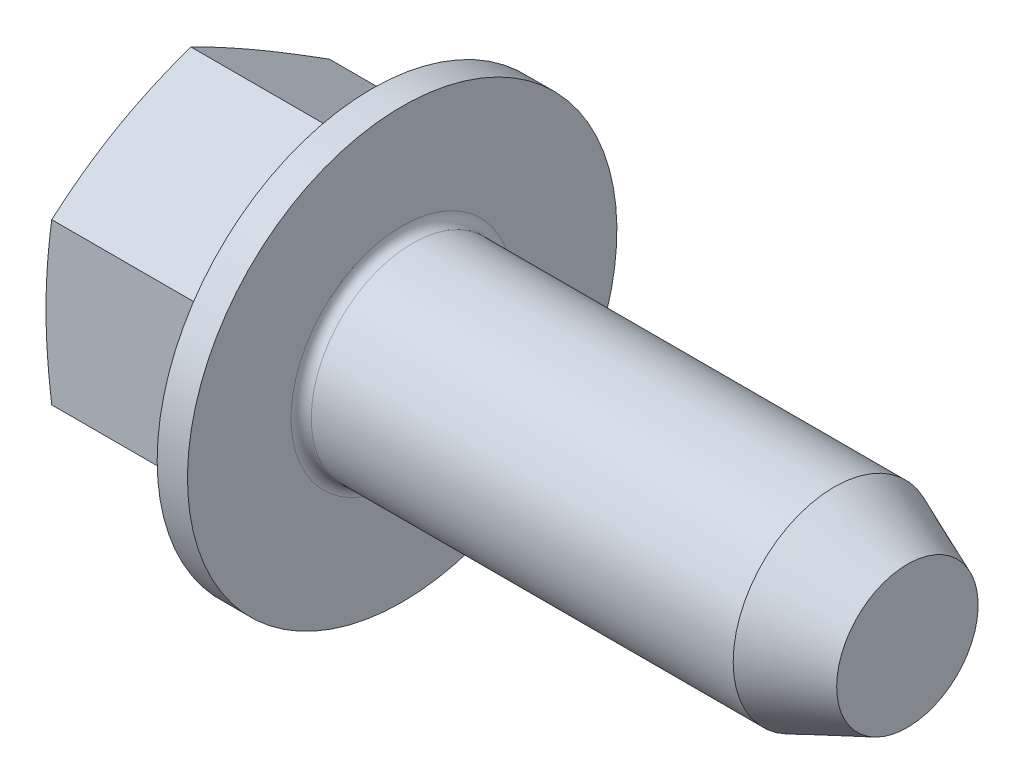
SolidWorks part; units mm, degrees
ref_plane "Front Plane" through (0, 0, 0) normal (0, 0, 1) x (1, 0, 0)
ref_plane "Top Plane" through (0, 0, 0) normal (0, 1, 0) x (1, 0, 0)
ref_plane "Right Plane" through (0, 0, 0) normal (1, 0, 0) x (0, 0, -1)
sketch "Sketch1" plane through (0, 0, 0) normal (0, 0, 1) x (1, 0, 0)
  line L0 (0, 0) -> (10, 0) construction
  line L1 (0, 0) -> (-4.3, 0) construction
  line L2 (0.2, 2) -> (9.61, 2)
  line L3 (10, 0) -> (10, 1.61)
  line L4 (0, 2.2) -> (0, 4.25)
  line L5 (0, 4.25) -> (-0.6, 4.25)
  line L6 (-0.6, 4.25) -> (-1.0019, 2.75)
  line L7 (-1.0019, 2.75) -> (-4.3, 2.75)
  line L8 (-4.3, 2.75) -> (-4.3, 2.2)
  line L9 (-4.3, 2.2) -> (-3.7625, 2.2)
  line L10 (-3.7625, 2.2) -> (-3.7625, 0)
  line L11 (-3.7625, 0) -> (10, 0)
  line L12 (-3.7625, 0) -> (-3.7625, 2.58) construction
  line L14 (10, 1.61) -> (9.61, 2)
  line L15 (10, 0) -> (0.7, 0) construction
  arc A0 (0.2, 2) -> (0, 2.2) centre (0.2, 2.2) cw
  dimension "D7" = 0.2
  dimension "K" = 4.3
  dimension "s" = 5.5
  dimension "dia" = 4
  dimension "D1" = 4.4
  dimension "D2" = 0.5375
  dimension "c" = 0.6
  dimension "D4" = 15
  dimension "D5" = 45
  dimension "min" = 3.22
  dimension "Dc" = 8.5
revolve "Revolve1" add sketch "Sketch1" angle 360 about L11
cosmetic thread "Cosmetic Thread1" [suppressed] parameters "D1"=14.01, "D2"=3.22
sketch "Sketch2" plane through (-4.3, 0, 0) normal (-1, 0, 0) x (0, 0, 1)
  line L1 (0, 3.1754) -> (-2.75, 1.5877)
  line L2 (-2.75, 1.5877) -> (-2.75, -1.5877)
  line L3 (-2.75, -1.5877) -> (0, -3.1754)
  line L4 (0, -3.1754) -> (2.75, -1.5877)
  line L5 (2.75, -1.5877) -> (2.75, 1.5877)
  line L6 (2.75, 1.5877) -> (0, 3.1754)
  circle A0 centre (0, 0) radius 2.2 construction
  circle A1 centre (0, 0) radius 2.2
  circle A2 centre (0, 0) radius 2.75 construction
  circle A3 centre (0, 0) radius 2.75 construction
extrude "Extrude1" add sketch "Sketch2" against normal up to next (4.3 mm away)
sketch "Sketch3" plane through (0, 0, 0) normal (0, 1, 0) x (1, 0, 0)
  line L0 (-4.6684, 1.375) -> (-3.9316, 4.125)
  line L1 (-4.3, 0) -> (-4.3, 2.75) construction
  line L2 (0, 0) -> (-3.6033, 0) construction
  line L3 (-3.9316, 4.125) -> (-4.6684, 4.125)
  line L4 (-4.6684, 4.125) -> (-4.6684, 1.375)
  dimension "D1" = 15
  dimension "D2" = 2.75
revolve "Cut-Revolve1" cut sketch "Sketch3" angle 360 about L2
fillet "Fillet1" radius 0.2 6 edges
sketch "Sketch4" plane through (0, 0, 0) normal (0, 0, 1) x (1, 0, 0)
  line L0 (0, 0) -> (5.3731, 0) construction
  line L1 (10, -1.61) -> (10, 1.61) construction
  line L3 (10, 1.4) -> (8.5515, 2)
  line L4 (0.2, 2) -> (9.61, 2) construction
  line L5 (8.5515, 2) -> (8.5515, 2.5)
  line L6 (8.5515, 2.5) -> (10, 2.5)
  line L7 (10, 2.5) -> (10, 1.4)
  dimension "D1" = 0.5
  dimension "D2" = 22.5
  dimension "Dp" = 2.8
revolve "Cut-Revolve2" cut sketch "Sketch4" angle 360 about L0
sketch "Sketch5" plane through (0, 0, 0) normal (0, 0, 1) x (1, 0, 0)
  line L0 (10, 0) -> (1.29, 0) construction
  line L1 (-3.7625, 0) -> (10, 0) construction
  line L2 (1.5152, 1.61) -> (1.7403, 2)
  line L3 (1.7403, 2) -> (1.7403, 2.4503)
  line L4 (1.7403, 2.4503) -> (1.29, 2.4503)
  line L5 (1.29, 2.4503) -> (1.29, 2)
  line L6 (1.29, 2) -> (1.5152, 1.61)
  dimension "B" = 14.01
  dimension "D1" = 3.22
  dimension "D2" = 4
revolve "Cut-Revolve10" [suppressed] cut sketch "Sketch5" angle 360 about L0
pattern_linear "LPattern10" [suppressed] count 21 spacing 0.7 along (1, 0, 0) of bodies 111
equation "\"D1@Sketch1\" = \"s@Sketch1\" / 10 * 8"
equation "\"D2@Sketch1\" = \"K@Sketch1\" / 8"
equation "\"D2@Sketch3\" = \"s@Sketch1\" / 2"
equation "\"D2@Cosmetic Thread1\" = \"min@Sketch1\""
equation "\"D1@Cosmetic Thread1\" = \"B@Sketch1\" -  ( \"dia@Sketch1\" - \"min@Sketch1\" )  / 2 - \"D7@Sketch1\""
equation "\"D1@Sketch5\" = \"D2@Cosmetic Thread1\""
equation "\"D2@Sketch5\" = \"dia@Sketch1\""
equation "\"B@Sketch5\" = \"D1@Cosmetic Thread1\""
equation "\"D1@LPattern10\" = int( \"D1@Cosmetic Thread1\" / \"D3@LPattern10\" + 0.999 ) "
